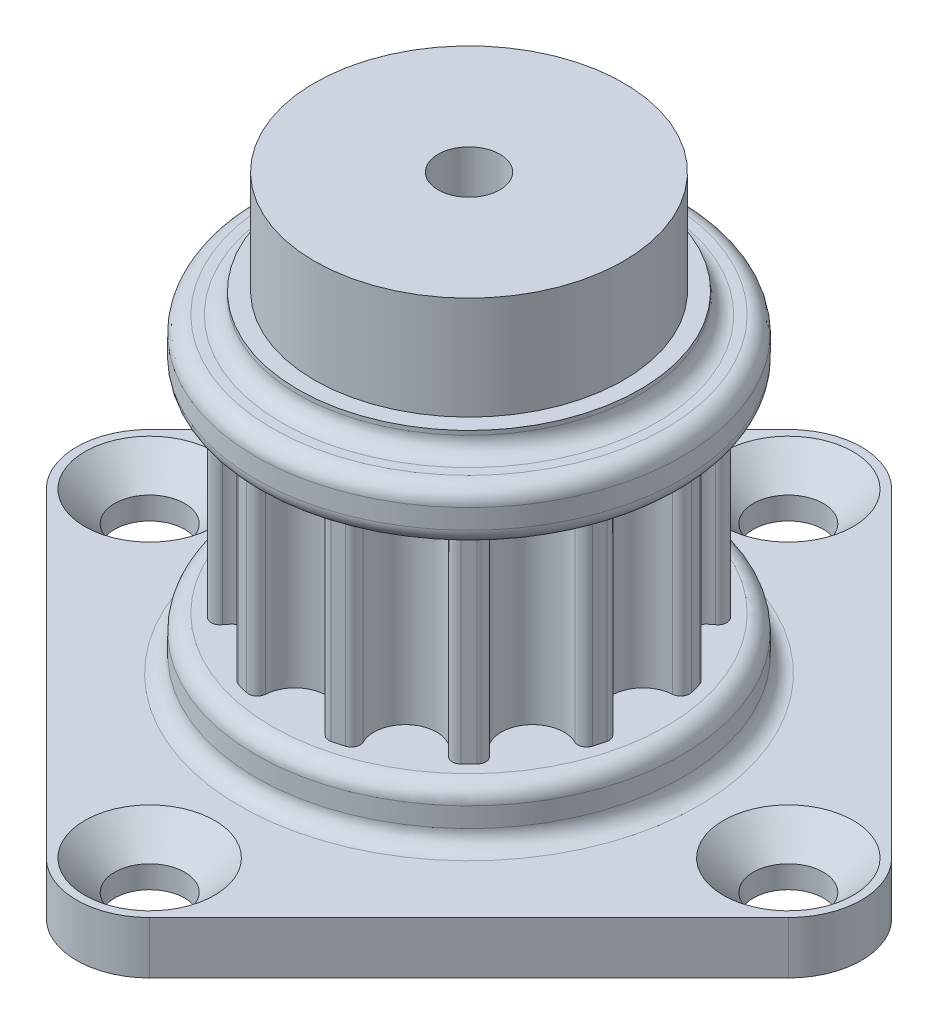
SolidWorks part; units mm, degrees
ref_plane "Front Plane" through (0, 0, 0) normal (0, 0, 1) x (1, 0, 0)
ref_plane "Top Plane" through (0, 0, 0) normal (0, 1, 0) x (1, 0, 0)
ref_plane "Right Plane" through (0, 0, 0) normal (1, 0, 0) x (0, 0, -1)
sketch "Sketch1" plane through (0, 0, 0) normal (0, 1, 0) x (1, 0, 0)
  line L0 (0, 0) -> (0, 8.9779) construction
  line L1 (0, 0) -> (4.2214, 7.3117) construction
  circle A0 centre (0, 0) radius 8.9779 construction
  circle A1 centre (0, 0) radius 6.9179 construction
  circle A2 centre (0, 8.4429) radius 1.525 construction
  circle A5 centre (4.2214, 7.3117) radius 1.525 construction
  arc A6 (0, 6.9179) -> (1.5221, 8.3487) centre (0, 8.4429) ccw
  arc A7 (1.5221, 8.3487) -> (2.0494, 8.7408) centre (1.9513, 8.3222) cw
  arc A8 (2.5955, 8.5945) -> (2.8562, 7.9912) centre (2.4712, 8.1828) cw
  arc A9 (3.4589, 5.991) -> (2.8562, 7.9912) centre (4.2214, 7.3117) cw
  arc A10 (2.0494, 8.7408) -> (2.5955, 8.5945) centre (0, 0) cw
  arc A11 (0, 6.9179) -> (3.4589, 5.991) centre (0, 0) ccw
  dimension "D1" = 17.9557
  dimension "D3" = 3.05
  dimension "D4" = 0.43
  dimension "D2" = 2.06
  dimension "D5" = 30
extrude "Boss-Extrude1" add sketch "Sketch1" along normal mid plane 10
ref_axis "Axis1" through (0, 3.3, 0) along (0, -1, 0)
pattern_circular "CirPattern1" count 12 over 360 about axis through (0, 3.3, 0) along (0, -1, 0) of "Boss-Extrude1"
sketch "Sketch2" plane through (0, -5, 0) normal (0, -1, 0) x (1, 0, 0)
  circle A0 centre (0, 0) radius 10.3431
  dimension "D1" = 20.6862
extrude "Boss-Extrude2" add sketch "Sketch2" along normal blind 2.54
mirror "Mirror1" about plane through (0, 0, 0) normal (0, 1, 0) of "Boss-Extrude2"
sketch "Sketch4" plane through (0, -7.54, 0) normal (0, -1, 0) x (1, 0, 0)
  line L0 (-15.5, 0) -> (0, 0) construction
  circle A0 centre (0, 0) radius 19.05
  circle A1 centre (-15.5, 0) radius 1.27
  dimension "D1" = 2.54
  dimension "D3" = 38.1
  dimension "D2" = 15.5
extrude "Boss-Extrude3" add sketch "Sketch4" along normal blind 2.54
sketch "Sketch6" plane through (0, -7.54, 0) normal (0, 1, 0) x (1, 0, 0)
  line L0 (15.5, 0) -> (0, -15.5) construction
  line L1 (15.5, 0) -> (0, 15.5) construction
  line L2 (0, -15.5) -> (-15.5, 0) construction
  line L3 (0, 15.5) -> (-15.5, 0) construction
  line L4 (15.5, 0) -> (-15.5, 0) construction
  line L5 (0, -15.5) -> (0, 15.5) construction
  circle A0 centre (0, -15.5) radius 1.27
  circle A1 centre (15.5, 0) radius 1.27
  circle A2 centre (0, 15.5) radius 1.27
  circle A3 centre (-15.5, 0) radius 1.27 construction
  circle A4 centre (-15.5, 0) radius 1.27
  point P1 (0, 0)
  point P20 (0, 0)
extrude "Cut-Extrude2" cut sketch "Sketch6" against normal through all both and the other way through all
hole_wizard "CSK for M3 Flat Head Machine Screw1" positions "3DSketch1" profile "Sketch7" countersink size "M3" standard "ANSI Metric" end condition through all
sketch3d "3DSketch1"
  line L0 (-15.5, -10.08, 0) -> (-15.5, -7.54, 0) construction
  line L1 (0, -10.08, 15.5) -> (0, -7.54, 15.5) construction
  line L2 (15.5, -10.08, 0) -> (15.5, -7.54, 0) construction
  line L3 (0, -10.08, -15.5) -> (0, -7.54, -15.5) construction
  point P0 (-15.5, -7.54, 0)
  point P4 (0, -7.54, 15.5)
  point P8 (15.5, -7.54, 0)
  point P12 (0, -7.54, -15.5)
sketch "Sketch7" plane through (-15.5, -7.54, 0) normal (1, 0, 0) x (0, 0, 1)
  line L0 (0, 0) -> (0, 2.54)
  line L1 (0, 2.54) -> (1.7, 2.54)
  line L2 (1.7, 2.54) -> (1.7, 1.45)
  line L3 (1.7, 1.45) -> (3.15, 0)
  line L5 (3.15, 0) -> (0, 0)
  line L6 (-1.7, 1.45) -> (-3.15, 0) construction
  line L11 (0, -6.35) -> (0, 107.95) construction
  dimension "Thru Hole Dia." = 3.4
  dimension "Thru Hole Depth" = 2.54
  dimension "Near C'Sink Dia." = 6.3
  dimension "Near C'Sink Angle" = 90
sketch "Sketch8" plane through (0, 7.54, 0) normal (0, 1, 0) x (1, 0, 0)
  circle A0 centre (0, 0) radius 7.5
  circle A1 centre (0, 0) radius 1.5
  dimension "D1" = 15
  dimension "D2" = 3
extrude "Boss-Extrude4" add sketch "Sketch8" along normal blind 6
sketch "Sketch9" plane through (0, 7.54, 0) normal (0, 1, 0) x (1, 0, 0)
  circle A0 centre (0, 0) radius 8.2937
  circle A1 centre (0, 0) radius 7.5 construction
  dimension "D1" = 0.7937
extrude "Boss-Extrude5" add sketch "Sketch9" along normal blind 1
sketch "Sketch10" plane through (0, -10.08, 0) normal (0, -1, 0) x (-1, 0, 0)
  line L0 (15.5, 0) -> (0, 15.5) construction
  line L1 (0, 15.5) -> (-15.5, 0) construction
  line L2 (-15.5, 0) -> (0, -15.5) construction
  line L3 (0, -15.5) -> (15.5, 0) construction
  line L4 (18.0102, 2.5102) -> (2.5102, 18.0102)
  line L5 (-2.5102, 18.0102) -> (-18.0102, 2.5102)
  line L6 (-18.0102, -2.5102) -> (-2.5102, -18.0102)
  line L7 (2.5102, -18.0102) -> (18.0102, -2.5102)
  line L8 (20.5205, 0) -> (0, 20.5205) construction
  line L9 (0, -20.5205) -> (20.5205, 0) construction
  line L10 (0, 20.5205) -> (-20.5205, 0) construction
  line L11 (-20.5205, 0) -> (0, -20.5205) construction
  arc A0 (2.5102, 18.0102) -> (-2.5102, 18.0102) centre (0, 15.5) ccw
  arc A1 (-18.0102, 2.5102) -> (-18.0102, -2.5102) centre (-15.5, 0) ccw
  circle A2 centre (0, 0) radius 19.05 construction
  arc A3 (-2.5102, -18.0102) -> (2.5102, -18.0102) centre (0, -15.5) ccw
  arc A4 (18.0102, 2.5102) -> (18.0102, -2.5102) centre (15.5, 0) cw
extrude "Cut-Extrude-Thin1" cut sketch "Sketch10" against normal through all flip side to cut thin thin type one direction wall 25.4
sketch "Sketch5" plane through (0, 0, 0) normal (0, 1, 0) x (1, 0, 0)
  circle A0 centre (0, 0) radius 1.5
  dimension "D1" = 3
extrude "Cut-Extrude1" cut sketch "Sketch5" against normal through all both and the other way through all
fillet "Fillet1" radius 0.7937 5 edges at (0, -7.54, -10.3431) (0, -5, -10.3431) (0, 5, -10.3431) (0, 7.54, -10.3431) (0, 7.54, 8.2937)
equation "\"TEETH_NUM\"= 12"
equation "\"TOOTH_PITCH\"= 5mm"
equation "\"PITCH_LINE_OFFSET\"= .5715mm"
equation "\"DIAMETER_PER_GROOVE\"= 1.59156mm"
equation "\"PITCH_DIAMETER\"= \"TEETH_NUM\" * \"DIAMETER_PER_GROOVE\""
equation "\"OUTSIDE_DIAMETER\"= \"PITCH_DIAMETER\" - \"PITCH_LINE_OFFSET\" * 2"
equation "\"D1@Sketch1\"=\"OUTSIDE_DIAMETER\""
equation "\"TOOTH_HEIGHT\"= 2.06mm"
equation "\"D2@Sketch1\"=\"TOOTH_HEIGHT\""
equation "\"TOOTH_DIAMETER\"= 3.05mm"
equation "\"INTERNAL_RADIUS\"= .43mm"
equation "\"D3@Sketch1\"=\"TOOTH_DIAMETER\""
equation "\"D5@Sketch1\"=360 / \"TEETH_NUM\""
equation "\"D4@Sketch1\"=\"INTERNAL_RADIUS\""
equation "\"D1@CirPattern1\"=\"TEETH_NUM\""
equation "\"D1@Sketch2\"=\"PITCH_DIAMETER\"+1/16"
equation "\"bearing_ID\"= 15mm"
equation "\"D1@Sketch8\"=\"bearing_ID\""
equation "\"center_ID\"= 3mm"
equation "\"D2@Sketch8\"=\"center_ID\""
equation "\"bearing_Height\"= 5mm"
equation "\"D1@Boss-Extrude4\"=\"bearing_Height\"+\"step_height\""
equation "\"step_height\"= 1mm"
equation "\"D1@Boss-Extrude5\"=\"step_height\""
equation "\"Pulley_Thicknes\"= 10mm"
equation "\"D1@Boss-Extrude1\"=\"Pulley_Thicknes\""
